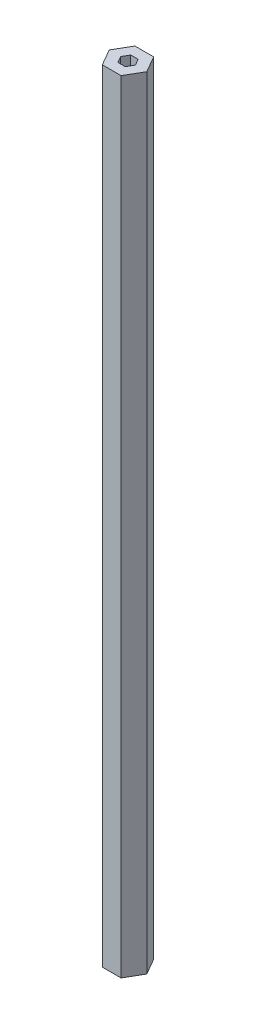
SolidWorks part; units mm, degrees
ref_plane "Front Plane" through (0, 0, 0) normal (0, 0, 1) x (1, 0, 0)
ref_plane "Top Plane" through (0, 0, 0) normal (0, 1, 0) x (1, 0, 0)
ref_plane "Right Plane" through (0, 0, 0) normal (1, 0, 0) x (0, 0, -1)
sketch "Sketch1" plane through (0, 0, 0) normal (0, 1, 0) x (1, 0, 0)
  line L9 (7.3323, 0) -> (3.6662, 6.35)
  line L10 (3.6662, 6.35) -> (-3.6662, 6.35)
  line L11 (-3.6662, 6.35) -> (-7.3323, 0)
  line L12 (-7.3323, 0) -> (-3.6662, -6.35)
  line L13 (-3.6662, -6.35) -> (3.6662, -6.35)
  line L14 (3.6662, -6.35) -> (7.3323, 0)
  line L15 (1.4434, 2.5) -> (-1.4434, 2.5)
  line L16 (-1.4434, 2.5) -> (-2.8868, 0)
  line L17 (-2.8868, 0) -> (-1.4434, -2.5)
  line L18 (-1.4434, -2.5) -> (1.4434, -2.5)
  line L19 (1.4434, -2.5) -> (2.8868, 0)
  line L20 (2.8868, 0) -> (1.4434, 2.5)
  circle A0 centre (0, 0) radius 6.35 construction
  circle A1 centre (0, 0) radius 2.5 construction
  dimension "D1" = 12.7
  dimension "D2" = 5
extrude "Boss-Extrude1" add sketch "Sketch1" along normal blind 304.8
